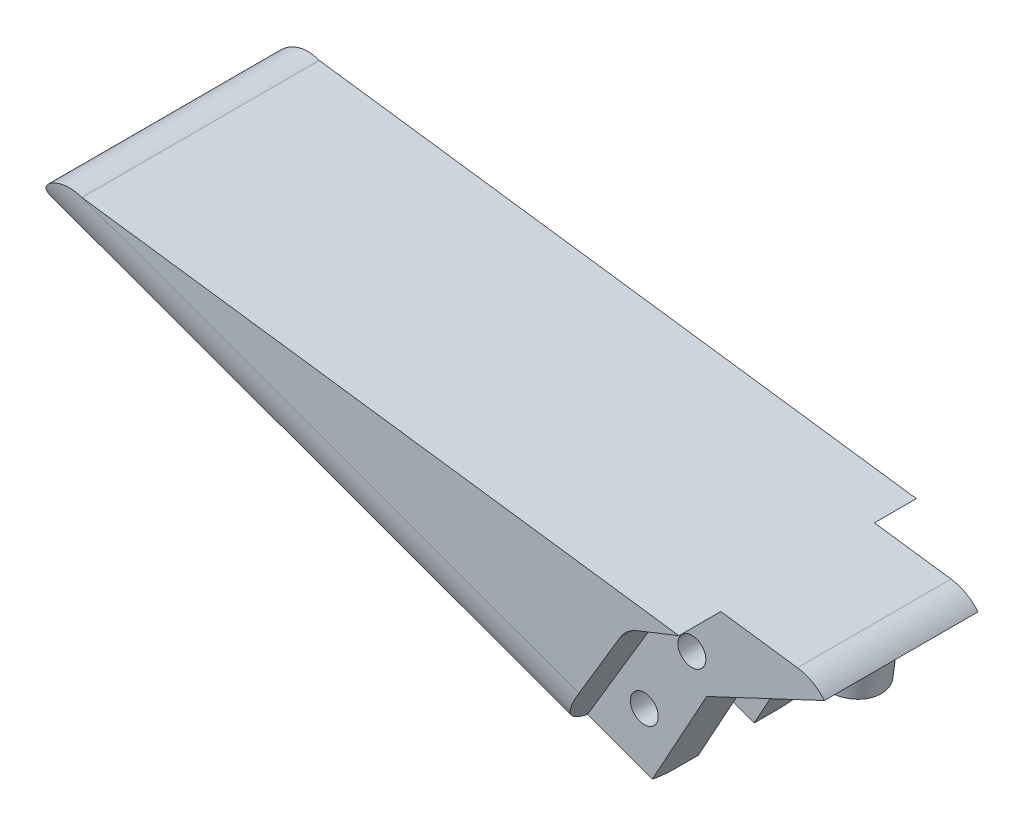
SolidWorks part; units mm, degrees
ref_plane "Спереди" through (0, 0, 0) normal (0, 0, 1) x (1, 0, 0)
ref_plane "Сверху" through (0, 0, 0) normal (0, 1, 0) x (1, 0, 0)
ref_plane "Справа" through (0, 0, 0) normal (1, 0, 0) x (0, 0, -1)
sketch "Sketch1" plane through (0, 0, 0) normal (0, 0, 1) x (1, 0, 0)
  line L0 (-11.0897, 53.4376) -> (-12.561, 47.6931)
  line L5 (-41.1485, 52.5176) -> (-50.5456, 55.9372)
  line L8 (-24.1858, 50.6705) -> (-25.5757, 46.8508)
  line L9 (-25.5757, 46.8508) -> (-67.8629, 62.2388)
  line L10 (-67.8629, 62.2388) -> (-66.1532, 66.9374)
  line L11 (-61.4546, 65.2276) -> (-13.2178, 58.6848)
  line L12 (-67.8629, 62.2388) -> (-63.1644, 60.5291)
  line L13 (-63.1644, 60.5291) -> (-61.4546, 65.2276) construction
  line L14 (-16.7674, 43.6456) -> (-41.1485, 52.5176)
  line L16 (-66.1532, 66.9374) -> (-61.4546, 65.2276) construction
  line L20 (-13.0487, 45.7891) -> (-12.561, 47.6931)
  line L21 (-10.6984, 54.9655) -> (-11.0897, 53.4376)
  circle A0 centre (-20.777, 55.9187) radius 1
  circle A1 centre (-24.1858, 50.6705) radius 1
  arc A2 (-16.7674, 43.6456) -> (-13.0487, 45.7891) centre (-15.9549, 46.5334) ccw
  arc A3 (-10.6984, 54.9655) -> (-13.2178, 58.6848) centre (-13.6046, 55.7098) ccw
  arc A7 (-61.4546, 65.2276) -> (-63.1644, 60.5291) centre (-62.3095, 62.8783) ccw
  dimension "D5" = 2
  dimension "D6" = 2
  dimension "D1" = 3
  dimension "D2" = 45
  dimension "D3" = 10
  dimension "D4" = 12
  dimension "D7" = 5
  dimension "D8" = 5
extrude "Boss-Extrude1" add sketch "Sketch1" along normal blind 17 contours L20 L0 L21 A0 A1 region at (-33.4896, 55.7393, 0)
ref_plane "Plane1" through (0, 0, 8.5) normal (0, 0, 1) x (1, 0, 0)
sketch "Sketch2" plane through (0, 0, 8.5) normal (0, 0, 1) x (1, 0, 0)
  line L0 (-24.5117, 53.1491) -> (-10.6984, 54.9655)
  line L1 (-26.6858, 50.6705) -> (-26.6858, 47.01)
  line L2 (-26.6858, 47.01) -> (-26.6858, 44.9809)
  line L3 (-10.6984, 54.9655) -> (-6.6778, 55.4941)
  line L4 (-6.6778, 55.4941) -> (-11.1613, 41.4543)
  line L5 (-11.1613, 41.4543) -> (-26.6858, 44.9809)
  arc A0 (-24.5117, 53.1491) -> (-26.6858, 50.6705) centre (-24.1858, 50.6705) ccw
  dimension "D1" = 5
extrude "Cut-Extrude1" cut sketch "Sketch2" against normal mid plane 4
sketch "Sketch3" plane through (0, 0, 17) normal (0, 0, 1) x (1, 0, 0)
  line L1 (-22.9237, 57.2001) -> (-29.1379, 46.7895)
  line L2 (-21.6972, 58.2432) -> (-16.9201, 60.1343)
  line L3 (-16.9201, 60.1343) -> (-5.8264, 57.7956)
  line L4 (-5.8264, 57.7956) -> (-12.3627, 40.0457)
  line L5 (-12.3627, 40.0457) -> (-29.1379, 46.7895)
  arc A0 (-21.6972, 58.2432) -> (-22.9237, 57.2001) centre (-20.777, 55.9187) ccw
  dimension "D1" = 5
extrude "Cut-Extrude2" cut sketch "Sketch3" against normal blind 3
mirror "Mirror1" about plane through (0, 0, 8.5) normal (0, 0, 1) of "Cut-Extrude2"
sketch "Sketch4" plane through (0, 0, 14) normal (0, 0, 1) x (1, 0, 0)
  line L4 (-19.7141, 53.6559) -> (-10.0798, 58.1815)
  line L5 (-19.7141, 53.6559) -> (-22.173, 49.1877)
  line L6 (-10.0798, 58.1815) -> (-11.2894, 40.1282)
  line L7 (-11.2894, 40.1282) -> (-24.5644, 44.8419)
  line L8 (-22.173, 49.1877) -> (-23.8121, 46.2091)
  line L9 (-16.7674, 43.6456) -> (-28.4722, 47.9048) construction
  line L10 (-23.8121, 46.2091) -> (-24.5644, 44.8419)
extrude "Cut-Extrude3" cut sketch "Sketch4" against normal through all
ref_plane "Plane2" through (7.0398, 51.9004, 0) normal (0.1344, 0.9909, 0) x (0.9909, -0.1344, 0)
sketch "Sketch5" plane through (7.0398, 51.9004, 0) normal (0.1344, 0.9909, 0) x (0.9909, -0.1344, 0)
  line L0 (-18.9284, -8.5) -> (-36.8686, -8.5) construction
  line L1 (-18.9284, -14) -> (-18.9284, -3) construction
  line L2 (-18.9284, -8.5) -> (-21.9284, -8.5) construction
  circle A0 centre (-21.9284, -8.5) radius 2
  circle A1 centre (-21.9284, -8.5) radius 1
  dimension "D2" = 4
  dimension "D3" = 2
  dimension "D1" = 3
extrude "Boss-Extrude2" add sketch "Sketch5" along normal blind 3
fillet "Fillet1" radius 5 2 edges at (-45.8183, 54.2169, 17) (-45.8183, 54.2169, 0)
